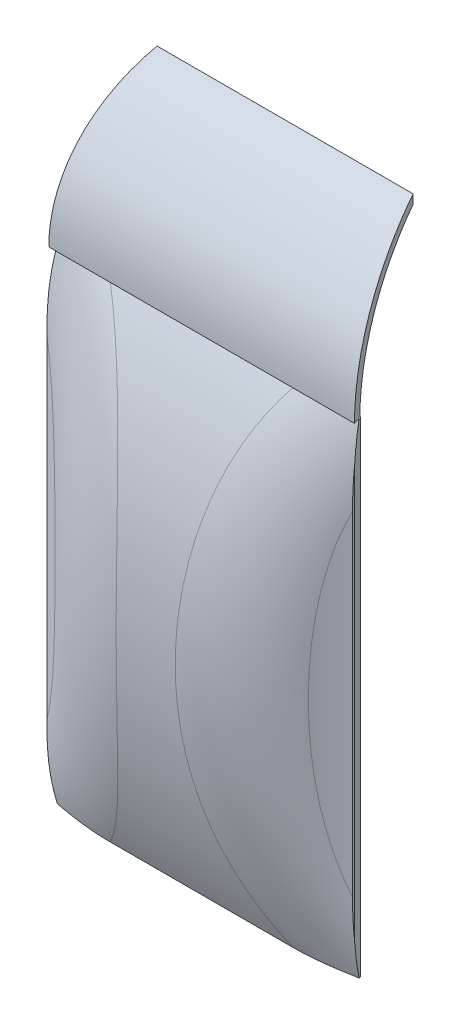
SolidWorks part; units mm, degrees
ref_plane "Front Plane" through (0, 0, 0) normal (0, 0, 1) x (1, 0, 0)
ref_plane "Top Plane" through (0, 0, 0) normal (0, 1, 0) x (1, 0, 0)
ref_plane "Right Plane" through (0, 0, 0) normal (1, 0, 0) x (0, 0, -1)
sketch "Sketch1" plane through (0, 0, 0) normal (0, 0, 1) x (1, 0, 0)
  line L1 (0, 0) -> (8.4, 0)
  line L2 (0, 0) -> (0, 13)
  line L3 (0, 13) -> (8.4, 13)
  line L4 (8.4, 0) -> (8.4, 13)
  dimension "D1" = 8.4
  dimension "D2" = 13
extrude "Boss-Extrude1" add sketch "Sketch1" along normal blind 0.24
ref_plane "Plane1" through (4.2, 0, 0) normal (1, 0, 0) x (0, 0, -1)
sketch "Sketch2" plane through (4.2, 0, 0) normal (1, 0, 0) x (0, 0, -1)
  line L0 (-0.24, 13) -> (-0.24, 0) construction
  line L1 (-0.24, 6.5) -> (-1.74, 6.5) construction
  line L2 (-0.24, 13) -> (-0.24, 0)
  arc A0 (-0.24, 13) -> (-0.24, 0) centre (13.0933, 6.5) ccw
  point P8 (-1.74, 6.5)
  point P9 (-1.74, 6.5)
  dimension "D1" = 1.5
extrude "Boss-Extrude2" add sketch "Sketch2" along normal mid plane 4
fillet "Fillet1" radius 4 2 edges at (6.2, 6.5, 0.24) (2.2, 6.5, 0.24)
fillet "Fillet3" radius 4 2 edges at (6.8296, 8.0585, 1.6579) (1.5704, 4.9415, 1.6579)
sketch "Sketch3" plane through (4.2, 0, 0) normal (1, 0, 0) x (0, 0, -1)
  line L2 (-0.0338, 13) -> (-0.0338, 15.8698) construction
  line L3 (2, 16.64) -> (2, 16.88)
  line L4 (-0.0338, 13) -> (-0.24, 13)
  arc A0 (-0.0338, 13) -> (2, 16.64) centre (4.2404, 13) cw
  arc A1 (2, 16.88) -> (-0.24, 13) centre (4.2404, 13) ccw
  dimension "D1" = 3.88
  dimension "D2" = 2.24
extrude "Boss-Extrude3" add sketch "Sketch3" along normal mid plane 8.2 contours A0 L3 A1 L4
sketch "Sketch4" plane through (0, 0, 0) normal (0, 1, 0) x (1, 0, 0)
  line L0 (0.1, -0.24) -> (8.3, -0.24) construction
  line L1 (8.3, -0.24) -> (7.4114, 2.76)
  line L2 (7.4114, 2.76) -> (0.9886, 2.76)
  line L3 (0.9886, 2.76) -> (0.1, -0.24)
  line L4 (0.1, -0.24) -> (-0.1586, -3.653)
  line L5 (-0.1586, -3.653) -> (8.3, -3.4588)
  line L6 (8.3, -3.4588) -> (8.3, -0.24)
  dimension "D1" = 73.5
  dimension "D2" = 73.5
  dimension "D3" = 3
extrude "Cut-Extrude2" cut sketch "Sketch4" along normal blind 20 flip side to cut contours L2 L3 L4 L5 L6 L1
